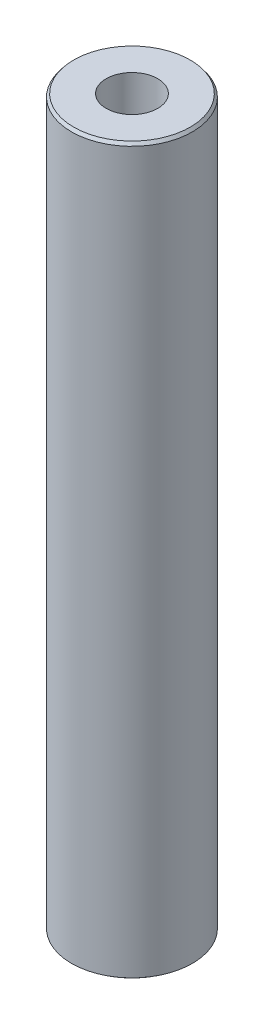
SolidWorks part; units mm, degrees
ref_plane "Front Plane" through (0, 0, 0) normal (0, 0, 1) x (1, 0, 0)
ref_plane "Top Plane" through (0, 0, 0) normal (0, 1, 0) x (1, 0, 0)
ref_plane "Right Plane" through (0, 0, 0) normal (1, 0, 0) x (0, 0, -1)
sketch "Sketch1" plane through (0, 0, 0) normal (0, 1, 0) x (1, 0, 0)
  circle A0 centre (0, 0) radius 50
  dimension "SHAFT_OD" = 100
extrude "Boss-Extrude1" add sketch "Sketch1" along normal blind 600
sketch "Sketch2" plane through (0, 0, 0) normal (0, 1, 0) x (1, 0, 0)
  circle A0 centre (0, 0) radius 21.3256
  dimension "BORE_D" = 42.6512
extrude "Cut-Extrude1" cut sketch "Sketch2" along normal through all
chamfer "Chamfer1" distance 2.4571 angle 36.586 2 edges at (0, 600, 50) (0, 0, 50) first distance on face at (0, 600, 50) first distance on face at (0, 0, 21.3256)
